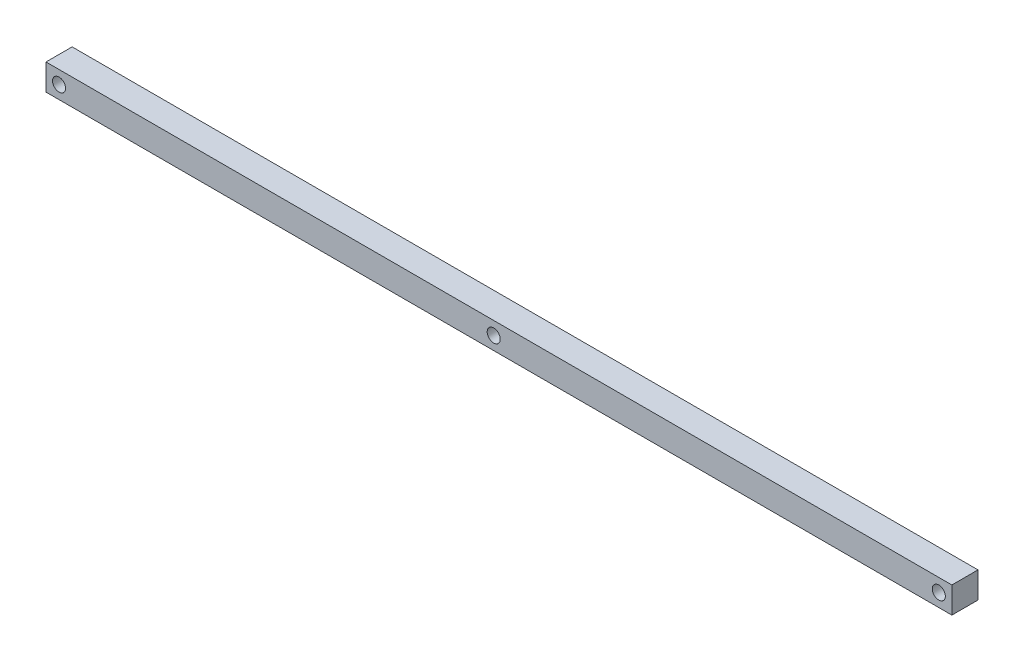
SolidWorks part; units mm, degrees
material "1060 Alloy for 162A"
ref_plane "Front Plane" through (0, 0, 0) normal (0, 0, 1) x (1, 0, 0)
ref_plane "Top Plane" through (0, 0, 0) normal (0, 1, 0) x (1, 0, 0)
ref_plane "Right Plane" through (0, 0, 0) normal (1, 0, 0) x (0, 0, -1)
sketch "Sketch1" plane through (0, 0, 0) normal (0, 0, 1) x (1, 0, 0)
  line L0 (505, 0) -> (-505, 0) construction
  line L1 (520, 15) -> (-520, 15)
  line L2 (520, 15) -> (520, -15)
  line L3 (520, -15) -> (-520, -15)
  line L4 (-520, 15) -> (-520, -15)
  line L5 (520, 15) -> (-520, -15) construction
  line L6 (520, -15) -> (-520, 15) construction
  circle A0 centre (-505, 0) radius 7.5
  circle A1 centre (505, 0) radius 7.5
  circle A2 centre (-6, 0) radius 7.5
  point P0 (0, 0)
  point P8 (0, 0)
  dimension "D2" = 15
  dimension "D1" = 30
  dimension "D3" = 1010
  dimension "D4" = 15
  dimension "D5" = 499
extrude "Boss-Extrude1" add sketch "Sketch1" along normal mid plane 30
equation "\"A\"= 202"
equation "\"hole_diameter\"=15"
equation "\"D2@Sketch1\"=\"hole_diameter\""
equation "\"D3@Sketch1\"=5*\"A\""
equation "\"D4@Sketch1\"=\"hole_diameter\""
equation "\"r15\"=499"
equation "\"D5@Sketch1\"=\"r15\""
